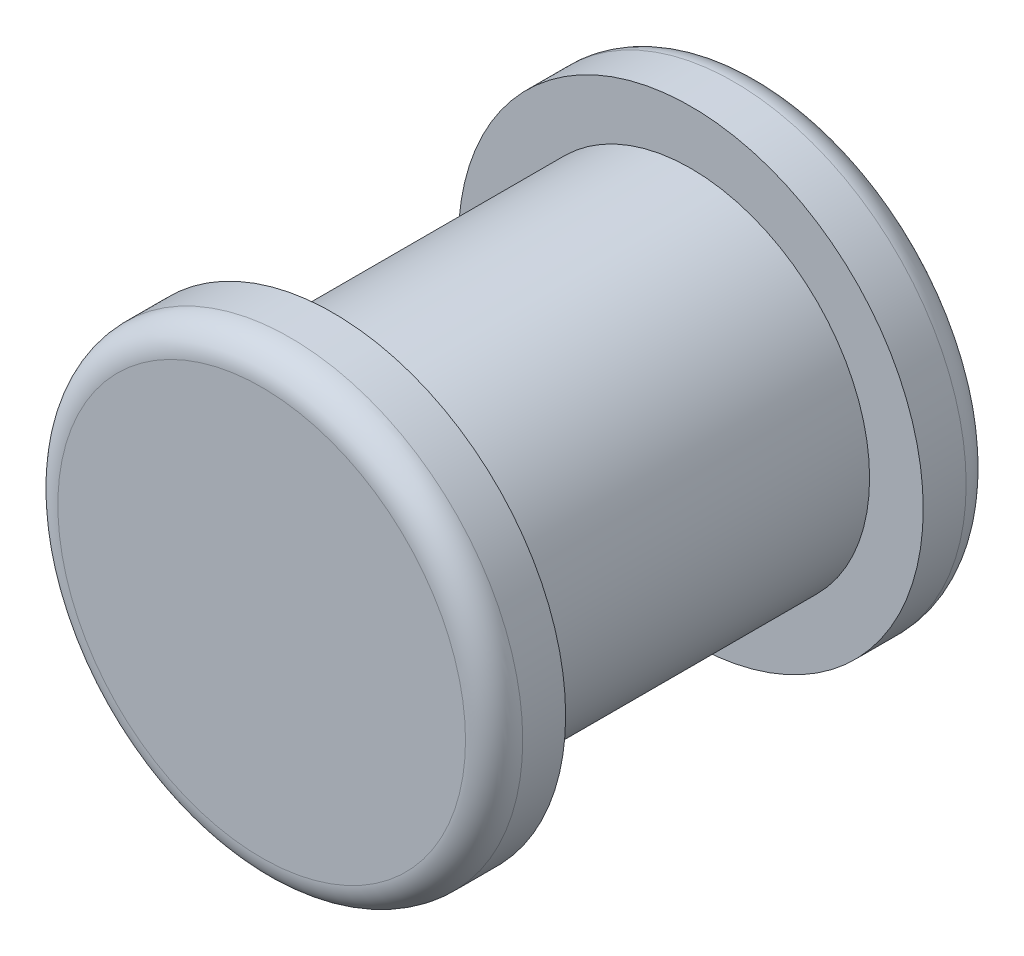
SolidWorks part; units mm, degrees
ref_plane "Front Plane" through (0, 0, 0) normal (0, 0, 1) x (1, 0, 0)
ref_plane "Top Plane" through (0, 0, 0) normal (0, 1, 0) x (1, 0, 0)
ref_plane "Right Plane" through (0, 0, 0) normal (1, 0, 0) x (0, 0, -1)
sketch "Sketch1" plane through (0, 0, 0) normal (0, 0, 1) x (1, 0, 0)
  circle A0 centre (0, 0) radius 250
  dimension "D1" = 500
extrude "Boss-Extrude1" add sketch "Sketch1" along normal blind 500 contours A0
sketch "Sketch2" plane through (0, 0, 500) normal (0, 0, 1) x (1, 0, 0)
  circle A0 centre (0, 0) radius 325
  dimension "D1" = 650
extrude "Boss-Extrude2" add sketch "Sketch2" along normal blind 100
sketch "Sketch3" plane through (0, 0, 0) normal (0, 0, -1) x (-1, 0, 0)
  circle A0 centre (0, 0) radius 325
  dimension "D1" = 650
extrude "Boss-Extrude3" add sketch "Sketch3" along normal blind 100
fillet "Fillet1" radius 40 2 edges at (325, 0, 600) (-325, 0, -100)
